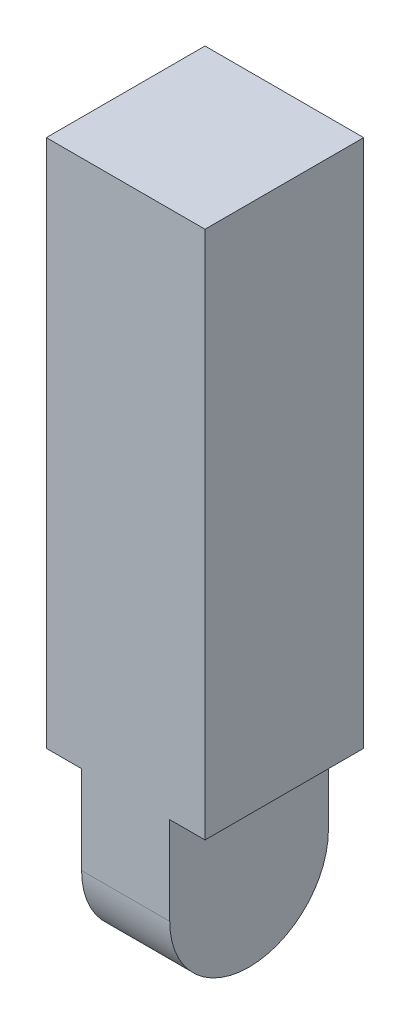
SolidWorks part; units mm, degrees
ref_plane "Front" through (0, 0, 0) normal (0, 0, 1) x (1, 0, 0)
ref_plane "Top" through (0, 0, 0) normal (0, 1, 0) x (1, 0, 0)
ref_plane "Right" through (0, 0, 0) normal (1, 0, 0) x (0, 0, -1)
sketch "草图1" plane through (0, 0, 0) normal (0, 1, 0) x (1, 0, 0)
  line L1 (-9, 9) -> (9, 9)
  line L2 (-9, 9) -> (-9, -9)
  line L3 (-9, -9) -> (9, -9)
  line L4 (9, 9) -> (9, -9)
  dimension "D1" = 18
  dimension "D2" = 18
  dimension "D3" = 9
  dimension "D4" = 9
extrude "凸台-拉伸1" add sketch "草图1" along normal blind 60
sketch "草图2" plane through (0, 0, 0) normal (1, 0, 0) x (0, 0, -1)
  line L5 (-9, -10) -> (-9, 1.0378)
  line L6 (-9, 1.0378) -> (9, 1.0378)
  line L7 (9, -10) -> (9, 1.0378)
  arc A1 (-9, -10) -> (9, -10) centre (0, -10) ccw
extrude "凸台-拉伸2" add sketch "草图2" along normal mid plane 10
